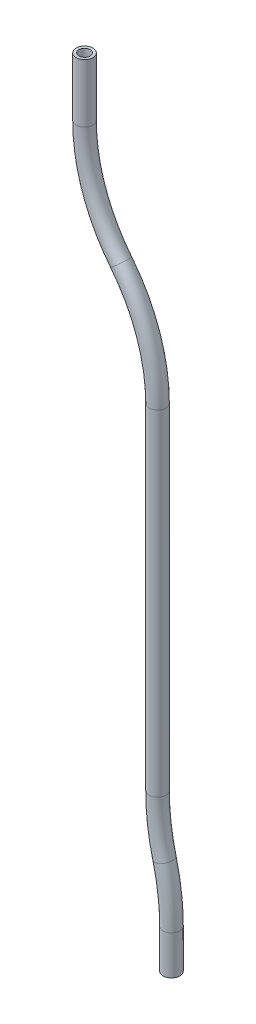
SolidWorks part; units mm, degrees
material "PET"
ref_plane "Спереди" through (0, 0, 0) normal (0, 0, 1) x (1, 0, 0)
ref_plane "Сверху" through (0, 0, 0) normal (0, 1, 0) x (1, 0, 0)
ref_plane "Справа" through (0, 0, 0) normal (1, 0, 0) x (0, 0, -1)
sketch "Эскиз1" plane through (0, 0, 0) normal (0, 1, 0) x (1, 0, 0)
  circle A0 centre (0, 0) radius 3
  circle A1 centre (0, 0) radius 2
  dimension "D1" = 6
  dimension "D2" = 4
extrude "Бобышка-Вытянуть1" add sketch "Эскиз1" along normal blind 15
sketch "Направляющая" plane through (0, 0, 0) normal (0, 0, 1) x (1, 0, 0)
  line L0 (0, 0) -> (0, -6)
  line L1 (26.2, -80.8436) -> (26.2, -201.1573)
  line L2 (31.2, -240.8436) -> (31.2, -254.8436)
  arc A0 (0, -6) -> (13.1, -43.4218) centre (60, -6) ccw
  arc A1 (13.1, -43.4218) -> (26.2, -80.8436) centre (-33.8, -80.8436) cw
  arc A2 (26.2, -201.1573) -> (28.7, -221.0004) centre (106.2, -201.1573) ccw
  arc A3 (31.2, -240.8436) -> (28.7, -221.0004) centre (-48.8, -240.8436) ccw
  dimension "D5" = 80
  dimension "D6" = 80
  dimension "D7" = 60
  dimension "D8" = 60
  dimension "D1" = 26.2
  dimension "D2" = 6
  dimension "D3" = 174
  dimension "D4" = 5
  dimension "D9" = 14
sweep "По траектории1" add profiles "Эскиз1<2>" path "Направляющая"
sketch "Эскиз1<2>" plane through (0, 0, 0) normal (0, 1, 0) x (1, 0, 0) same geometry as "Эскиз1"
